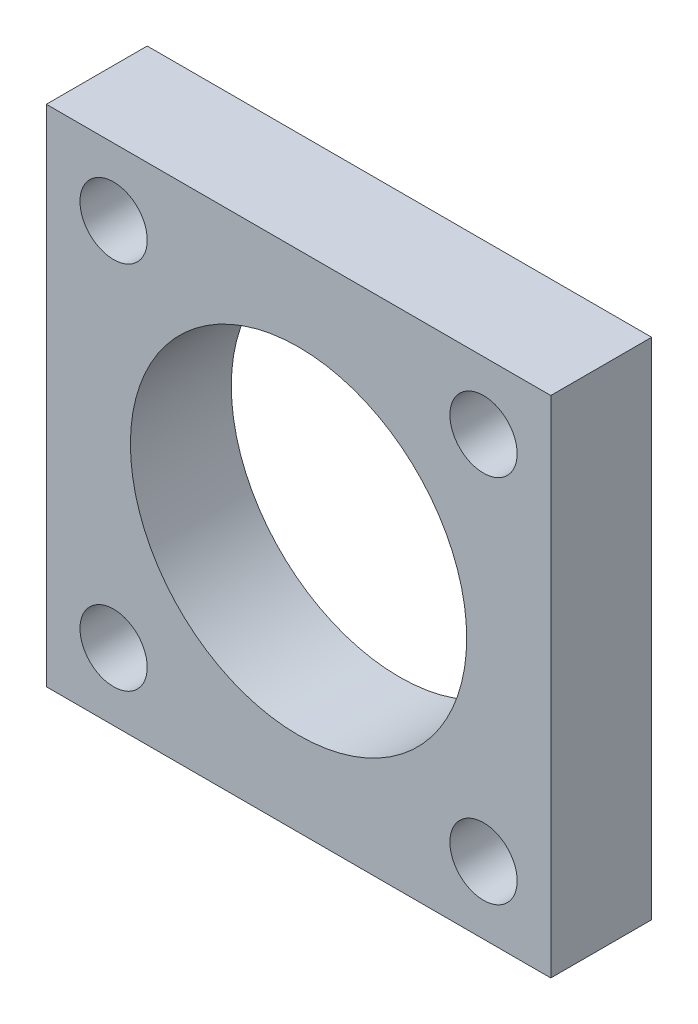
SolidWorks part; units mm, degrees
material "AISI 316 Annealed Stainless Steel Bar (SS)"
ref_plane "Front Plane" through (0, 0, 0) normal (0, 0, 1) x (1, 0, 0)
ref_plane "Top Plane" through (0, 0, 0) normal (0, 1, 0) x (1, 0, 0)
ref_plane "Right Plane" through (0, 0, 0) normal (1, 0, 0) x (0, 0, -1)
sketch "Sketch1" plane through (0, 0, 0) normal (0, 0, 1) x (1, 0, 0)
  line L1 (-15, -15) -> (15, -15)
  line L2 (-15, -15) -> (-15, 15)
  line L3 (-15, 15) -> (15, 15)
  line L4 (15, -15) -> (15, 15)
  line L5 (-15, -15) -> (15, 15) construction
  line L6 (-15, 15) -> (15, -15) construction
  circle A0 centre (0, 0) radius 10
  circle A1 centre (-11, 11) radius 2
  circle A2 centre (11, 11) radius 2
  circle A3 centre (11, -11) radius 2
  circle A4 centre (-11, -11) radius 2
  point P0 (0, 0)
  point P19 (0, 0)
  dimension "D1" = 20
  dimension "D2" = 4
  dimension "D5" = 4
  dimension "D6" = 4
  dimension "D3" = 30
  dimension "D4" = 30
extrude "Boss-Extrude1" add sketch "Sketch1" along normal blind 6 contours A4 L2 L1 L4 A2 L3 A3 A1 A0 region at (-14.5757, 0, 0)
